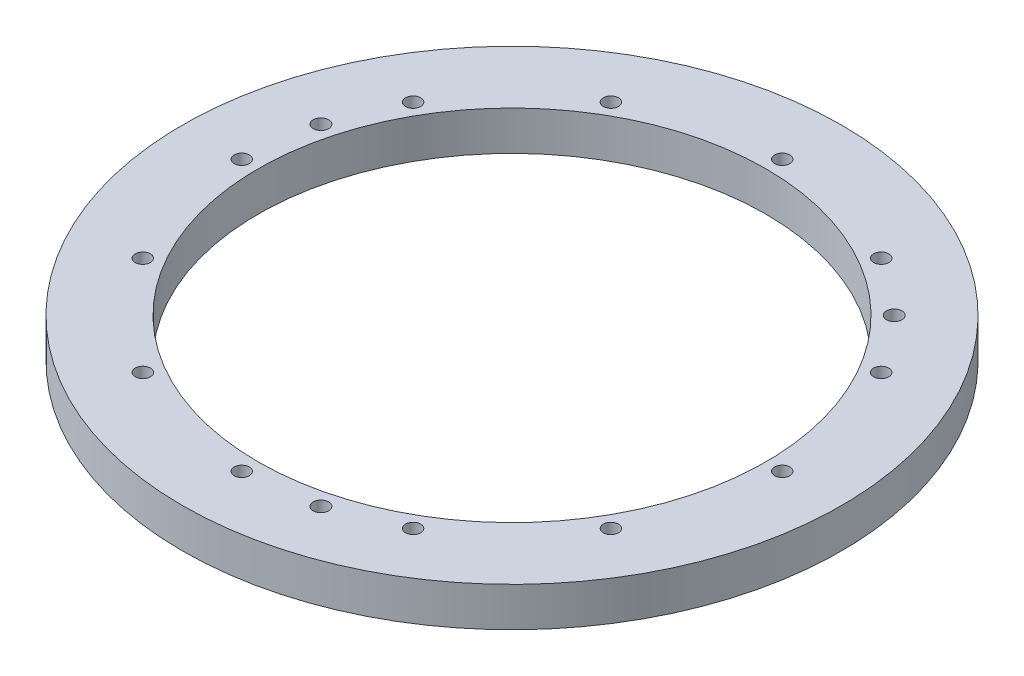
SolidWorks part; units mm, degrees
material "6061 Alloy"
ref_plane "Front Plane" through (0, 0, 0) normal (0, 0, 1) x (1, 0, 0)
ref_plane "Top Plane" through (0, 0, 0) normal (0, 1, 0) x (1, 0, 0)
ref_plane "Right Plane" through (0, 0, 0) normal (1, 0, 0) x (0, 0, -1)
sketch "Sketch1" plane through (0, 0, 0) normal (0, 1, 0) x (1, 0, 0)
  circle A0 centre (0, 0) radius 49.2125
  circle A1 centre (0, 0) radius 63.881
  circle A3 centre (0, -52.3875) radius 1.4732
  circle A4 centre (-26.1938, -45.3689) radius 1.4732
  circle A5 centre (-45.3689, -26.1937) radius 1.4732
  circle A6 centre (-52.3875, 0) radius 1.4732
  circle A7 centre (-45.3689, 26.1938) radius 1.4732
  circle A8 centre (-26.1937, 45.3689) radius 1.4732
  circle A9 centre (0, 52.3875) radius 1.4732
  circle A10 centre (26.1938, 45.3689) radius 1.4732
  circle A11 centre (45.3689, 26.1937) radius 1.4732
  circle A12 centre (52.3875, 0) radius 1.4732
  circle A13 centre (45.3689, -26.1938) radius 1.4732
  circle A14 centre (26.1937, -45.3689) radius 1.4732
  point P21 (0, 0)
  dimension "D1" = 98.425
  dimension "D4" = 2.9464
  dimension "D5" = 52.3875
  dimension "D2" = 14.6685
  dimension "D6" = 12
extrude "Boss-Extrude1" add sketch "Sketch1" along normal blind 7.62 contours A0 | A1 region at (-62.0742, 0, 0)
sketch "Sketch2" plane through (0, 7.62, 0) normal (0, 1, 0) x (1, 0, 0)
  circle A0 centre (-45.3689, 26.1938) radius 1.4732 construction
  circle A1 centre (-52.3875, 0) radius 1.4732 construction
  circle A2 centre (-45.3689, 26.1938) radius 1.4732 construction
  circle A3 centre (-52.3875, 0) radius 1.4732 construction
  arc A4 (-52.3875, 0) -> (-45.3689, 26.1938) centre (0, 0) cw construction
  circle A5 centre (-50.6024, 13.5589) radius 1.5
  dimension "D1" = 3
extrude "Cut-Extrude1" cut sketch "Sketch2" against normal through all
pattern_circular "CirPattern1" count 3 over 360 about axis through (0, 7.62, 0) along (0, 1, 0) of "Cut-Extrude1"
equation "\"Middle Coupler Inner Daimeter\"= 3.875in"
equation "\"Middle Coupler  Wall Thickness\" = 0.25in"
equation "\"Middle Coupler Bottom Thickness\"= 0.2in"
equation "\"Bearing Rail Offset\"= 0.45in"
equation "\"3-56 UNF Tap\"= 0.089in"
equation "\"3-56 UNF Clearance\"= 0.104in"
equation "\"D5@Sketch1\"=(\"Middle Coupler Inner Daimeter\"*2+0.5)/4in"
equation "\"Ball Bearing Distance\"= 0.03in"
equation "\"D4@Sketch1\"=\"4-40 Clearance\""
equation "\"D1@Sketch1\"=\"Middle Coupler Inner Daimeter\""
equation "\"TCA Outer Diameter\" = 6in"
equation "\"Interstage Aeroframe Wall Thickness\" = 0.072in"
equation "\"Compression Spring OD\"= 0.42in"
equation "\"10-24 Tap\"= 0.1495in"
equation "\"10-24 Clearance\"= 0.196in"
equation "\"Lower Stage Fuselage Wall Thickness\" = 0.25in"
equation "\"6-32 Tap\" = 0.107in"
equation "\"1/4-20 Tap\" = 0.201in"
equation "\"D2@Sketch1\"=0.5875 - 10/1000"
equation "\"D1@Sketch2\"=3mm"
equation "\"3-48 Tap\"= 0.079in"
equation "\"4-40 Tap\"= 0.089in"
equation "\"3-48 Clearance\" = 0.104in"
equation "\"4-40 Clearance\" = 0.116in"
equation "\"6-32 Clearance\" = 0.144in"
equation "\"12-24 Tap\" = 0.177in"
equation "\"12-24 Major Diameter\"= 0.216in"
